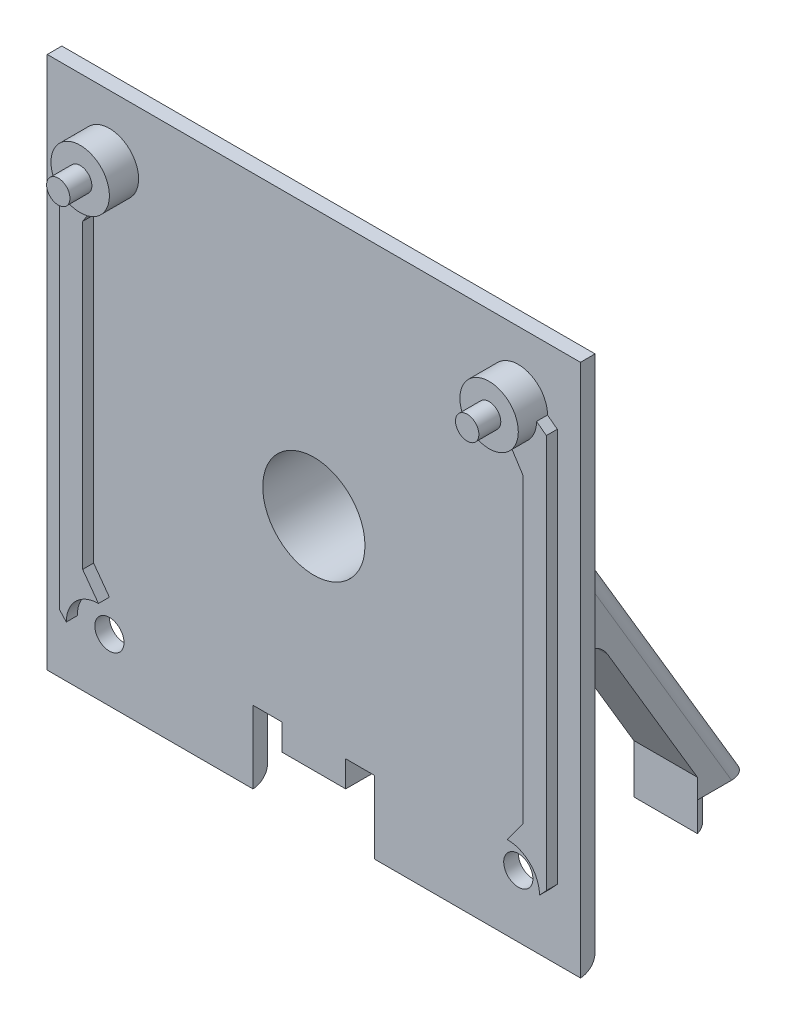
SolidWorks part; units mm, degrees
ref_plane "Front Plane" through (0, 0, 0) normal (0, 0, 1) x (1, 0, 0)
ref_plane "Top Plane" through (0, 0, 0) normal (0, 1, 0) x (1, 0, 0)
ref_plane "Right Plane" through (0, 0, 0) normal (1, 0, 0) x (0, 0, -1)
sketch "Sketch1" plane through (0, 0, 0) normal (0, 0, 1) x (1, 0, 0)
  line L0 (0, 0) -> (36.5125, 0)
  line L1 (0, 0) -> (0, 36.5125)
  line L2 (36.5125, 0) -> (36.5125, 36.5125)
  line L3 (36.5125, 36.5125) -> (0, 36.5125)
extrude "Extrude1" add sketch "Sketch1" along normal blind 1
sketch "Sketch2" plane through (0, 0, 1) normal (0, 0, 1) x (1, 0, 0)
  line L0 (0, 36.5125) -> (36.5125, 0) construction
  line L1 (36.5125, 36.5125) -> (0, 0) construction
  circle A0 centre (32.2563, 32.2563) radius 2
  circle A1 centre (4.2562, 32.2563) radius 2
  point P8 (4.2562, 32.2563)
  point P9 (18.2563, 18.2562)
  point P10 (32.2563, 32.2563)
  point P11 (32.2563, 4.2563)
  point P12 (4.2563, 4.2563)
  dimension "D1" = 14
  dimension "D2" = 14
  dimension "D3" = 14
  dimension "D4" = 14
extrude "Extrude2" add sketch "Sketch2" along normal blind 2
sketch "Sketch3" plane through (0, 0, 1) normal (0, 0, 1) x (1, 0, 0)
  line L0 (1.5875, 4.7625) -> (1.5875, 31.75)
  line L1 (0, 36.5125) -> (36.5125, 0) construction
  line L2 (36.5125, 0) -> (36.5125, 36.5125) construction
  line L3 (36.5125, 36.5125) -> (0, 0) construction
  line L4 (1.5875, 31.75) -> (2.2562, 32.2563)
  line L5 (2.0563, 4.2563) -> (1.5875, 4.7625)
  line L6 (34.925, 4.7625) -> (34.925, 31.75)
  line L7 (34.925, 4.7625) -> (34.4563, 4.2562)
  line L8 (32.2563, 6.4562) -> (33.3375, 7.9375)
  line L9 (33.3375, 7.9375) -> (33.3375, 28.575)
  line L10 (33.3375, 28.575) -> (32.2563, 30.2562)
  line L11 (4.2563, 6.4563) -> (3.175, 7.9375)
  line L12 (3.175, 7.9375) -> (3.175, 28.575)
  line L13 (3.175, 28.575) -> (4.2562, 30.2562)
  line L14 (34.925, 31.75) -> (34.2563, 32.2563)
  line L15 (2.2562, 32.2563) -> (4.2562, 30.2562)
  line L16 (32.2563, 30.2562) -> (34.2563, 32.2563)
  circle A0 centre (32.2563, 4.2562) radius 2.2 construction
  circle A1 centre (4.2563, 4.2563) radius 2.2 construction
  arc A2 (4.2563, 6.4563) -> (2.0563, 4.2563) centre (4.2563, 4.2563) ccw
  arc A3 (32.2563, 6.4562) -> (34.4563, 4.2562) centre (32.2563, 4.2562) cw
  circle A5 centre (4.2562, 32.2563) radius 2 construction
  circle A6 centre (4.2562, 32.2563) radius 2 construction
  arc A7 (32.2563, 30.2562) -> (34.2563, 32.2563) centre (32.2563, 32.2563) ccw construction
  circle A8 centre (32.2563, 32.2563) radius 2 construction
  circle A9 centre (32.2563, 32.2563) radius 2 construction
  point P11 (32.2563, 4.2562)
  point P12 (4.2563, 4.2563)
  point P13 (18.2562, 18.2563)
  dimension "D1" = 14
  dimension "D2" = 14
extrude "Extrude3" add sketch "Sketch3" along normal blind 0.75
sketch "Sketch4" plane through (0, 0, 1) normal (0, 0, 1) x (1, 0, 0)
  line L0 (0, 36.5125) -> (36.5125, 0) construction
  line L1 (0, 0) -> (36.5125, 36.5125) construction
  line L2 (36.5125, 0) -> (36.5125, 36.5125) construction
  circle A0 centre (32.2563, 4.2562) radius 1
  circle A1 centre (4.2563, 4.2563) radius 1
  point P9 (18.2563, 18.2562)
  point P10 (4.2563, 4.2563)
  point P11 (32.2563, 4.2562)
  dimension "D1" = 14
  dimension "D2" = 14
extrude "Extrude4" cut sketch "Sketch4" against normal through all
sketch "Sketch5" plane through (0, 0, 3) normal (0, 0, 1) x (1, 0, 0)
  circle A0 centre (32.2563, 32.2563) radius 0.8
  circle A1 centre (4.2562, 32.2563) radius 0.8
extrude "Extrude5" add sketch "Sketch5" along normal blind 1.5
sketch "Sketch6" plane through (0, 0, 0) normal (0, 0, -1) x (-1, 0, 0)
  line L0 (-22.425, 0) -> (-22.425, 4.9625)
  line L1 (0, 0) -> (-36.5125, 0) construction
  line L2 (-16.075, 3.175) -> (-16.075, 4.9625)
  line L3 (-20.4375, 3.175) -> (-20.4375, 4.9625)
  line L4 (-14.0875, 4.9625) -> (-16.075, 4.9625)
  line L5 (-20.4375, 4.9625) -> (-22.425, 4.9625)
  line L6 (-20.4375, 3.175) -> (-16.075, 3.175)
  line L7 (-14.0875, 4.9625) -> (-14.0875, 0)
  line L8 (-14.0875, 0) -> (-22.425, 0)
extrude "Extrude6" cut sketch "Sketch6" against normal through all
sketch "Sketch7" plane through (0, 0, 0) normal (0, 0, -1) x (-1, 0, 0)
  line L0 (-20.4375, 3.175) -> (-16.075, 3.175)
  line L1 (-16.075, 3.175) -> (-16.075, 6.175)
  line L2 (-20.4375, 6.175) -> (-16.075, 6.175)
  line L4 (-20.4375, 3.175) -> (-20.4375, 6.175)
extrude "Extrude7" add sketch "Sketch7" along normal blind 19
sketch "Sketch8" plane through (20.4375, 0, 0) normal (1, 0, 0) x (0, 0, -1)
  line L0 (19, 4.7486) -> (19, 0) construction
  line L2 (19, 6.175) -> (19, 3.175) construction
  line L3 (19, 4.7486) -> (19, 0)
  line L4 (19, 0) -> (11, 0)
  line L5 (11, 0) -> (19, 4.7486)
extrude "Extrude8" cut sketch "Sketch8" against normal through all
sketch "Sketch9" plane through (0, -4.8282, -2.8659) normal (0, -0.8599, -0.5104) x (1, 0, 0)
  line L0 (14.3195, -18) -> (22.225, -18) construction
  line L2 (16.075, -18) -> (16.075, -15.6794)
  line L3 (16.075, -18) -> (20.4375, -18)
  line L4 (20.4375, -18) -> (20.4375, -15.6794)
  line L5 (16.075, -18.7623) -> (16.075, -15.6794) construction
  line L6 (20.4375, -18.7623) -> (20.4375, -15.6794) construction
  line L8 (20.4375, -15.6794) -> (16.075, -15.6794)
extrude "Extrude9" add sketch "Sketch9" along normal blind 17 and the other way blind 36
sketch "Sketch10" plane through (20.4375, 0, 0) normal (1, 0, 0) x (0, 0, -1)
  line L0 (28.575, -9.525) -> (22.225, -9.525)
  line L1 (22.225, -9.525) -> (22.225, -13)
  line L2 (22.225, -13) -> (28.575, -13)
  line L3 (28.575, -13) -> (28.575, -9.525)
extrude "Extrude10" cut sketch "Sketch10" against normal through all
sketch "Sketch11" plane through (0, 0, 0) normal (0, 0, -1) x (-1, 0, 0)
  line L0 (-36.5125, 36.5125) -> (0, 0) construction
  line L1 (-36.5125, 0) -> (0, 36.5125) construction
  circle A0 centre (-18.2563, 18.2563) radius 4.5
  point P7 (-18.2563, 18.2563)
extrude "Extrude11" add sketch "Sketch11" along normal blind 12
sketch "Sketch12" plane through (0, 0, -12) normal (0, 0, -1) x (-1, 0, 0)
  line L0 (-22.7563, 18.2563) -> (-21.2563, 18.2563)
  line L1 (-15.2563, 18.2563) -> (-13.7563, 18.2563)
  arc A0 (-13.7563, 18.2563) -> (-22.7563, 18.2563) centre (-18.2563, 18.2563) ccw
  arc A1 (-16.075, 14.3202) -> (-20.4375, 14.3202) centre (-18.2563, 18.2563) ccw construction
  circle A2 centre (-18.2563, 18.2563) radius 3 construction
  arc A3 (-21.2563, 18.2563) -> (-15.2563, 18.2563) centre (-18.2563, 18.2563) ccw
extrude "Extrude12" cut sketch "Sketch12" against normal blind 4.2
sketch "Sketch13" plane through (16.075, 0, 0) normal (-1, 0, 0) x (0, 0, 1)
  line L0 (-6.5115, 24.2946) -> (-19.745, 2)
  line L1 (0, 35.2645) -> (-7.7594, 22.1923) construction
  line L2 (-12, 15.0481) -> (-17.2668, 6.175) construction
  line L3 (-19.745, 2) -> (-19.745, 23.3821)
  line L4 (-19.745, 23.3821) -> (-6.5115, 24.2946)
extrude "Extrude13" cut sketch "Sketch13" against normal through all and the other way blind 4.5
sketch "Sketch15" plane through (0, 0, 1) normal (0, 0, 1) x (1, 0, 0)
  line L0 (0, 36.5125) -> (36.5125, 0) construction
  line L1 (36.5125, 36.5125) -> (0, 0) construction
  circle A0 centre (18.2563, 18.2562) radius 3.5
  point P8 (18.2563, 18.2562)
extrude "Extrude14" cut sketch "Sketch15" against normal blind 7.5
sketch "Sketch16" plane through (0, 0, -6.5) normal (0, 0, 1) x (1, 0, 0)
  circle A0 centre (18.2563, 18.2562) radius 0.5
extrude "Extrude15" cut sketch "Sketch16" against normal blind 0.3
sketch "Sketch17" plane through (0, -9.525, 0) normal (0, -1, 0) x (1, 0, 0)
  line L0 (0, 0) -> (36.5125, 1) construction
  line L1 (36.5125, 0) -> (0, 1) construction
  line L2 (18.2562, 0.5) -> (18.2562, -38.7052) construction
  line L3 (0, 1) -> (14.0875, 1) construction
  line L4 (11.1125, -23.09) -> (26.9875, -23.09) construction
  line L5 (16.075, -16.3489) -> (16.075, -23.8874) construction
  line L6 (16.075, -23.09) -> (20.4375, -23.09)
  circle A0 centre (18.2563, -22.39) radius 2.3 construction
  arc A1 (16.075, -23.09) -> (20.4375, -23.09) centre (18.2563, -22.39) ccw
  point P8 (18.2563, 0.5)
  point P11 (18.2563, -22.39)
  dimension "D2" = 0.7
  dimension "D1" = 23.39
extrude "Extrude16" add sketch "Sketch17" along normal blind 2 separate body
sketch "Sketch18" plane through (0, -9.525, 0) normal (0, -1, 0) x (1, 0, 0)
  line L0 (20.4375, -26.586) -> (20.4375, -23.09)
  line L1 (20.4375, -23.09) -> (16.075, -23.09)
  line L2 (16.075, -23.09) -> (16.075, -26.586)
  line L3 (16.075, -26.586) -> (20.4375, -26.586)
extrude "Extrude17" add sketch "Sketch18" against normal blind 5
sketch "Sketch19" plane through (20.4375, 0, 0) normal (1, 0, 0) x (0, 0, -1)
  line L0 (19.0739, 3.1307) -> (28.2339, -12.3012)
  line L1 (12, 15.0481) -> (23.6181, -4.525) construction
  line L2 (28.2339, -12.3012) -> (26.9875, 3.175)
  line L3 (26.9875, 3.175) -> (19.0739, 3.1307)
extrude "Extrude18" cut sketch "Sketch19" against normal through all
fillet "Fillet2" radius 1 12 edges at (14.0875, 0, 0.5) (22.425, 0, 0.5) (20.4375, 28.7284, -3.8797) (20.4375, 2.7615, -19.293) (16.075, 28.7284, -3.8797) (16.075, 2.7615, -19.293) (20.4375, 14.6842, -12) (16.075, 14.6842, -12) (7.0438, 0, 0) (36.5125, 0, 0.5) (0, 0, 0.5) (29.4688, 0, 0)
fillet "Fillet3" radius 2 7 edges at (18.2563, 6.175, 0) (18.2563, 3.175, -16.3489) (18.2563, 6.175, -14.5682)
sketch "Sketch20" plane through (16.075, 0, 0) normal (-1, 0, 0) x (0, 0, 1)
  line L0 (1, 34.7414) -> (1, 32.4028)
  line L1 (2.0265, 34.1321) -> (1, 32.4028) construction
  line L2 (1, 36.5125) -> (1, 0) construction
  line L3 (1, 32.4028) -> (2.0265, 34.1321)
  line L4 (2.0265, 34.1321) -> (1, 34.7414)
extrude "Extrude19" cut sketch "Sketch20" against normal up to surface (4.3625 mm away) up to face at (20.4375, 33.7588, 1.3422)
